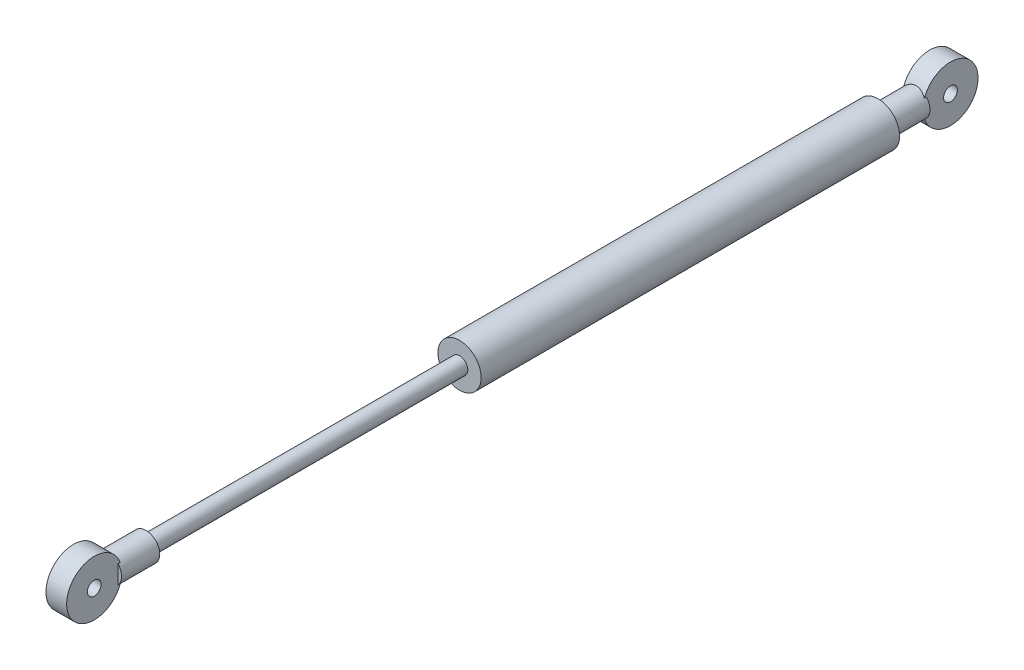
SolidWorks part; units mm, degrees
ref_plane "Front Plane" through (0, 0, 0) normal (0, 0, 1) x (1, 0, 0)
ref_plane "Top Plane" through (0, 0, 0) normal (0, 1, 0) x (1, 0, 0)
ref_plane "Right Plane" through (0, 0, 0) normal (1, 0, 0) x (0, 0, -1)
sketch "Sketch1" plane through (0, 0, 0) normal (1, 0, 0) x (0, 0, -1)
  line L0 (-186.1818, 0) -> (0, 0) construction
  line L1 (-13.5, 3) -> (-5.1962, 3)
  line L2 (-13.5, 3) -> (-13.5, 0)
  line L5 (-5.1962, 3) -> (-5.1962, 0)
  line L6 (-172.6818, 1.8) -> (-104.5, 1.8)
  line L7 (-13.5, 0) -> (0, 0)
  line L8 (-13.5, 0) -> (-104.5, 0)
  line L9 (-13.5, 0) -> (-13.5, 4.7)
  line L10 (-13.5, 4.7) -> (-104.5, 4.7)
  line L11 (-104.5, 0) -> (-104.5, 4.7)
  line L12 (-13.5, 0) -> (-104.5, 4.7) construction
  line L13 (-13.5, 4.7) -> (-104.5, 0) construction
  line L14 (-186.1818, 0) -> (-172.6818, 0)
  line L16 (-180.9856, 3) -> (-172.6818, 3)
  line L17 (-172.6818, 0) -> (-172.6818, 3)
  line L18 (-172.6818, 0) -> (-104.5, 0)
  line L19 (-180.9856, 0) -> (-180.9856, 3)
  circle A0 centre (-186.1818, 0) radius 1.5
  circle A1 centre (0, 0) radius 1.5
  circle A2 centre (0, 0) radius 6
  circle A3 centre (-186.1818, 0) radius 6
  point P15 (-59, 2.35)
  dimension "D1" = 3
  dimension "D2" = 12
  dimension "D7" = 12
  dimension "D3" = 3
  dimension "D4" = 4.7
  dimension "D5" = 13.5
  dimension "D6" = 91
  dimension "D8" = 13.5
  dimension "D9" = 3
  dimension "D10" = 1.8
extrude "Boss-Extrude1" add sketch "Sketch1" along normal mid plane 4.5 contours A3 A0 | L7 A2 L5 A1 | L5 A2 L7 | L14 A3 L19 region at (0, 5.6316, -1.509) region at (0, 1.1358, 5.5196) region at (0, -1.509, 191.8134) region at (0, 1.1358, 180.6621)
revolve "Revolve1" add sketch "Sketch1<3>" angle 360 about L8 region at (0, 1.5255, 9.6162) region at (0, 2.35, 59)
sketch "Sketch1<3>" plane through (0, 0, 0) normal (1, 0, 0) x (0, 0, -1) same geometry as "Sketch1"
revolve "Revolve2" add sketch "Sketch1<62>" angle 360 about L18 region at (0, 0.9, 138.5909) region at (0, 1.5255, 176.5655) region at (0, 1.1358, 180.6621)
sketch "Sketch1<62>" plane through (0, 0, 0) normal (1, 0, 0) x (0, 0, -1) same geometry as "Sketch1"
combine bodies "Combine1" operation type add bodies to combine 105 101
